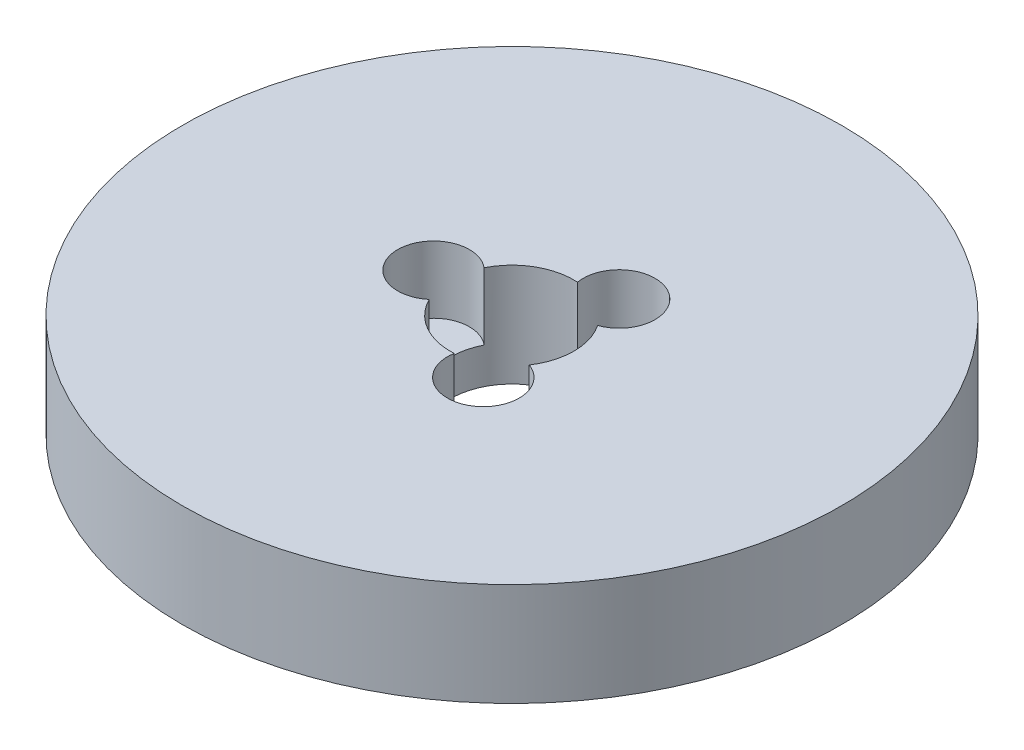
SolidWorks part; units mm, degrees
ref_plane "Front Plane" through (0, 0, 0) normal (0, 0, 1) x (1, 0, 0)
ref_plane "Top Plane" through (0, 0, 0) normal (0, 1, 0) x (1, 0, 0)
ref_plane "Right Plane" through (0, 0, 0) normal (1, 0, 0) x (0, 0, -1)
sketch "Sketch1" plane through (0, 0, 0) normal (0, 1, 0) x (1, 0, 0)
  circle A0 centre (0, 0) radius 80
  dimension "FLANGE_OD" = 160
extrude "Boss-Extrude1" add sketch "Sketch1" along normal blind 25
sketch "Sketch2" plane through (0, 0, 0) normal (0, 1, 0) x (1, 0, 0)
  circle A0 centre (0, 0) radius 15
  dimension "BORE_D" = 30
extrude "Cut-Extrude1" cut sketch "Sketch2" along normal through all
sketch "Sketch3" plane through (0, 25, 0) normal (0, 1, 0) x (1, 0, 0)
  circle A0 centre (0, 0) radius 19.041 construction
  circle A1 centre (-19.041, 0) radius 8.7079
  dimension "BOLT_D" = 17.4159
  dimension "BOLT_PCD" = 38.0821
extrude "Cut-Extrude2" cut sketch "Sketch3" against normal blind 16.2438
pattern_circular "CirPattern1" count 3 over 360 about axis through (0, 0, 0) along (0, 1, 0) of "Cut-Extrude2"
